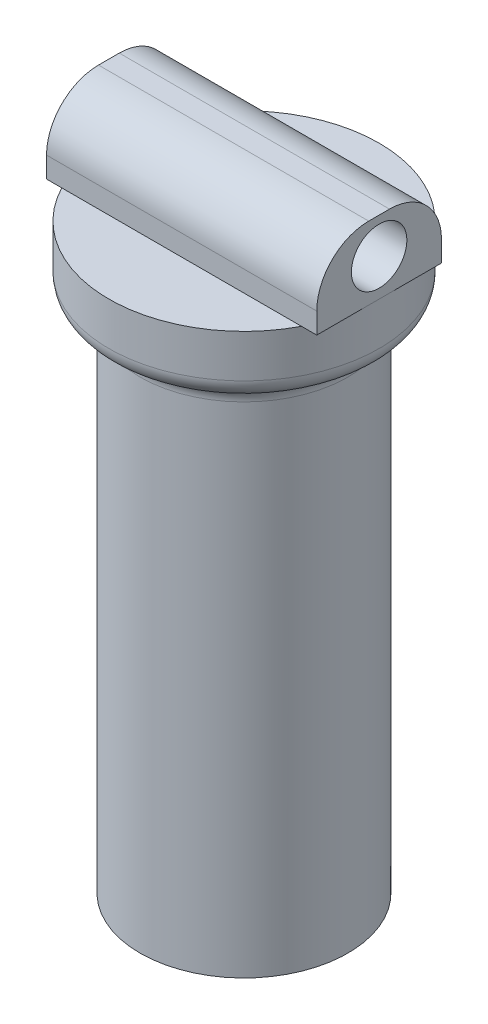
SolidWorks part; units mm, degrees
ref_plane "Front Plane" through (0, 0, 0) normal (0, 0, 1) x (1, 0, 0)
ref_plane "Top Plane" through (0, 0, 0) normal (0, 1, 0) x (1, 0, 0)
ref_plane "Right Plane" through (0, 0, 0) normal (1, 0, 0) x (0, 0, -1)
sketch "Sketch1" plane through (0, 0, 0) normal (0, 1, 0) x (1, 0, 0)
  circle A0 centre (0, 0) radius 65
  dimension "D1" = 130
extrude "Boss-Extrude1" add sketch "Sketch1" along normal blind 30
sketch "Sketch2" plane through (0, 0, 0) normal (0, -1, 0) x (1, 0, 0)
  circle A0 centre (0, 0) radius 50
  dimension "D1" = 100
extrude "Boss-Extrude2" add sketch "Sketch2" along normal blind 250
fillet "Fillet1" radius 10 1 edges at (0, 0, 50)
fillet "Fillet2" radius 10 1 edges at (0, 0, 65)
sketch "Sketch3" plane through (0, 0, 0) normal (1, 0, 0) x (0, 0, -1)
  line L0 (65, 30) -> (-65, 30) construction
  line L1 (-30, 30) -> (30, 30)
  line L2 (-30, 30) -> (-30, 65)
  line L3 (-30, 65) -> (30, 65)
  line L4 (30, 30) -> (30, 65)
  dimension "D1" = 60
  dimension "D2" = 35
  dimension "D3" = 35
extrude "Boss-Extrude3" add sketch "Sketch3" along normal mid plane 130
sketch "Sketch4" plane through (65, 0, 0) normal (1, 0, 0) x (0, 0, -1)
  circle A0 centre (0, 47.8975) radius 13.35
  dimension "D1" = 26.7
extrude "Cut-Extrude1" cut sketch "Sketch4" against normal blind 130
fillet "Fillet3" radius 25 2 edges at (0, 65, -30) (0, 65, 30)
